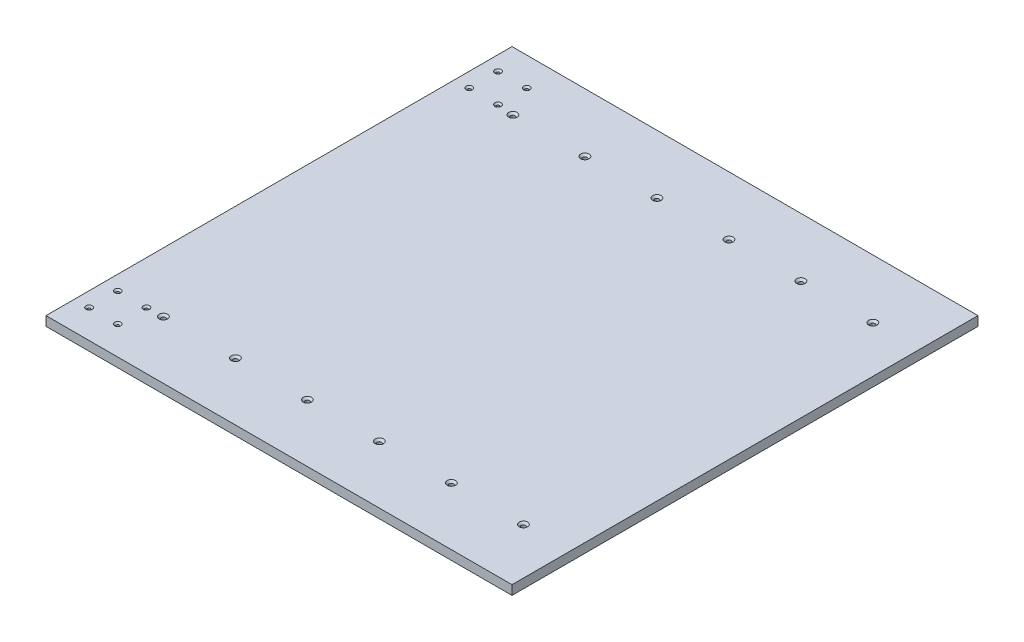
SolidWorks part; units mm, degrees
material "Buk"
ref_plane "Płaszczyzna przednia" through (0, 0, 0) normal (0, 0, 1) x (1, 0, 0)
ref_plane "Płaszczyzna górna" through (0, 0, 0) normal (0, 1, 0) x (1, 0, 0)
ref_plane "Płaszczyzna prawa" through (0, 0, 0) normal (1, 0, 0) x (0, 0, -1)
sketch "Szkic1" plane through (0, 0, 0) normal (0, 1, 0) x (1, 0, 0)
  line L1 (0, 0) -> (500, 0)
  line L2 (0, 0) -> (0, 500)
  line L3 (0, 500) -> (500, 500)
  line L4 (500, 0) -> (500, 500)
  dimension "D1" = 500
extrude "Dodanie-wyciągnięcie1" add sketch "Szkic1" along normal blind 10
sketch "Szkic2" plane through (0, 10, 0) normal (0, 1, 0) x (1, 0, 0)
  line L0 (0, 0) -> (500, 0) construction
  line L1 (0, 500) -> (0, 0) construction
  line L2 (0, 250) -> (500, 250) construction
  line L3 (500, 0) -> (500, 500) construction
  circle A0 centre (15.6, 30.6) radius 1.6
  circle A1 centre (15.6, 61.4) radius 1.6
  circle A2 centre (46.4, 61.4) radius 1.6
  circle A3 centre (46.4, 30.6) radius 1.6
  circle A4 centre (15.6, 438.6) radius 1.6
  circle A5 centre (15.6, 469.4) radius 1.6
  circle A6 centre (46.4, 469.4) radius 1.6
  circle A7 centre (46.4, 438.6) radius 1.6
  dimension "D1" = 3.2
  dimension "D2" = 3.2
  dimension "D3" = 3.2
  dimension "D4" = 3.2
  dimension "D5" = 30.6
  dimension "D6" = 30.6
  dimension "D7" = 30.8
  dimension "D8" = 15.6
  dimension "D9" = 15.6
  dimension "D10" = 30.8
  dimension "D11" = 30.8
  dimension "D12" = 30.8
hole_wizard "Pogłębienie stożkowe pod M3 Wkręt ustalający1" positions "Szkic3" profile "Szkic5" countersink size "M3" standard "Ansi Metric"
sketch "Szkic3" plane through (0, 10, 0) normal (0, 1, 0) x (1, 0, 0)
  point P0 (46.4, 30.6)
  point P3 (46.4, 61.4)
  point P6 (15.6, 61.4)
  point P9 (15.6, 30.6)
  point P12 (46.4, 438.6)
  point P15 (46.4, 469.4)
  point P18 (15.6, 469.4)
  point P21 (15.6, 438.6)
sketch "Szkic5" plane through (46.4, 10, -30.6) normal (1, 0, 0) x (0, 0, 1)
  line L0 (0, 0) -> (0, 11.0215)
  line L1 (0, 11.0215) -> (1.7, 10)
  line L2 (1.7, 10) -> (1.7, 1.66)
  line L3 (1.7, 1.66) -> (3.36, 0)
  line L5 (3.36, 0) -> (0, 0)
  line L6 (-1.7, 1.66) -> (-3.36, 0) construction
  line L10 (0, 11.0215) -> (-1.7, 10) construction
  line L11 (0, -6.35) -> (0, 107.95) construction
  dimension "Œrednica otworu" = 3.4
  dimension "G³êbokoœc otworu" = 10
  dimension "Œrednica zewnêtrznego pog³êbienia sto¿kowego" = 6.72
  dimension "K¹t zewnêtrznego pog³êbienia sto¿kowego" = 90
  dimension "K¹t wiert³a" = 118
hole_wizard "Pogłębienie stożkowe pod M4 Wkręt ustalający1" positions "Szkic6" profile "Szkic7" countersink size "M4" standard "Ansi Metric"
sketch "Szkic6" plane through (0, 10, 0) normal (0, 1, 0) x (1, 0, 0)
  line L0 (0, 500) -> (0, 0) construction
  line L1 (0, 0) -> (500, 0) construction
  point P0 (63.9, 62.07)
  point P14 (141.15, 62.07)
  point P15 (218.4, 62.07)
  point P16 (295.65, 62.07)
  point P17 (372.9, 62.07)
  point P18 (450.15, 62.07)
  point P19 (141.15, 437.07)
  point P20 (218.4, 437.07)
  point P21 (295.65, 437.07)
  point P22 (372.9, 437.07)
  point P23 (450.15, 437.07)
  point P24 (63.9, 437.07)
  dimension "D1" = 63.9
  dimension "D2" = 62.07
  dimension "D3" = 6
  dimension "D4" = 2
sketch "Szkic7" plane through (63.9, 10, -62.07) normal (1, 0, 0) x (0, 0, 1)
  line L0 (0, 0) -> (0, 12.9421)
  line L1 (0, 12.9421) -> (2.4, 11.5)
  line L2 (2.4, 11.5) -> (2.4, 2.08)
  line L3 (2.4, 2.08) -> (4.48, 0)
  line L5 (4.48, 0) -> (0, 0)
  line L6 (-2.4, 2.08) -> (-4.48, 0) construction
  line L10 (0, 12.9421) -> (-2.4, 11.5) construction
  line L11 (0, -6.35) -> (0, 107.95) construction
  dimension "Œrednica otworu" = 4.8
  dimension "G³êbokoœc otworu" = 11.5
  dimension "Œrednica zewnêtrznego pog³êbienia sto¿kowego" = 8.96
  dimension "K¹t zewnêtrznego pog³êbienia sto¿kowego" = 90
  dimension "K¹t wiert³a" = 118
sketch "Szkic8" plane through (0, 0, 0) normal (0, -1, 0) x (1, 0, 0)
  line L0 (0, -500) -> (0, 0) construction
  line L1 (60, -37) -> (460, -37)
  line L2 (60, -37) -> (60, -47)
  line L3 (60, -47) -> (460, -47)
  line L4 (460, -37) -> (460, -47)
  line L5 (0, 0) -> (500, 0) construction
  line L6 (60, -77) -> (60, -87)
  line L7 (60, -77) -> (460, -77)
  line L8 (460, -77) -> (460, -87)
  line L9 (60, -87) -> (460, -87)
  line L10 (60, -452) -> (60, -462)
  line L11 (60, -462) -> (460, -462)
  line L12 (460, -452) -> (460, -462)
  line L13 (60, -452) -> (460, -452)
  line L14 (60, -412) -> (60, -422)
  line L15 (60, -412) -> (460, -412)
  line L16 (460, -412) -> (460, -422)
  line L17 (60, -422) -> (460, -422)
  dimension "D1" = 10
  dimension "D2" = 400
  dimension "D3" = 60
  dimension "D4" = 2
  dimension "37" = 37
  dimension "D5" = 10
  dimension "D6" = 375
extrude "Wytnij-wyciągnięcie1" cut sketch "Szkic8" against normal blind 1
fillet "Zaokrąglenie1" radius 2 16 edges at (460, 1, -457) (260, 1, -462) (60, 1, -457) (260, 1, -452) (460, 1, -417) (260, 1, -422) (60, 1, -417) (260, 1, -412) (460, 1, -82) (260, 1, -87) (60, 1, -82) (260, 1, -77) (260, 1, -37) (460, 1, -42) (260, 1, -47) (60, 1, -42)
sketch "Sketch1" plane through (0, 0, 0) normal (0, -1, 0) x (1, 0, 0)
  line L0 (0, 0) -> (500, 0) construction
  line L1 (500, 0) -> (500, -500) construction
  circle A0 centre (468, -46) radius 5
  dimension "D1" = 46
  dimension "D2" = 10
  dimension "D3" = 32
extrude "Cut-Extrude1" cut sketch "Sketch1" against normal blind 4
